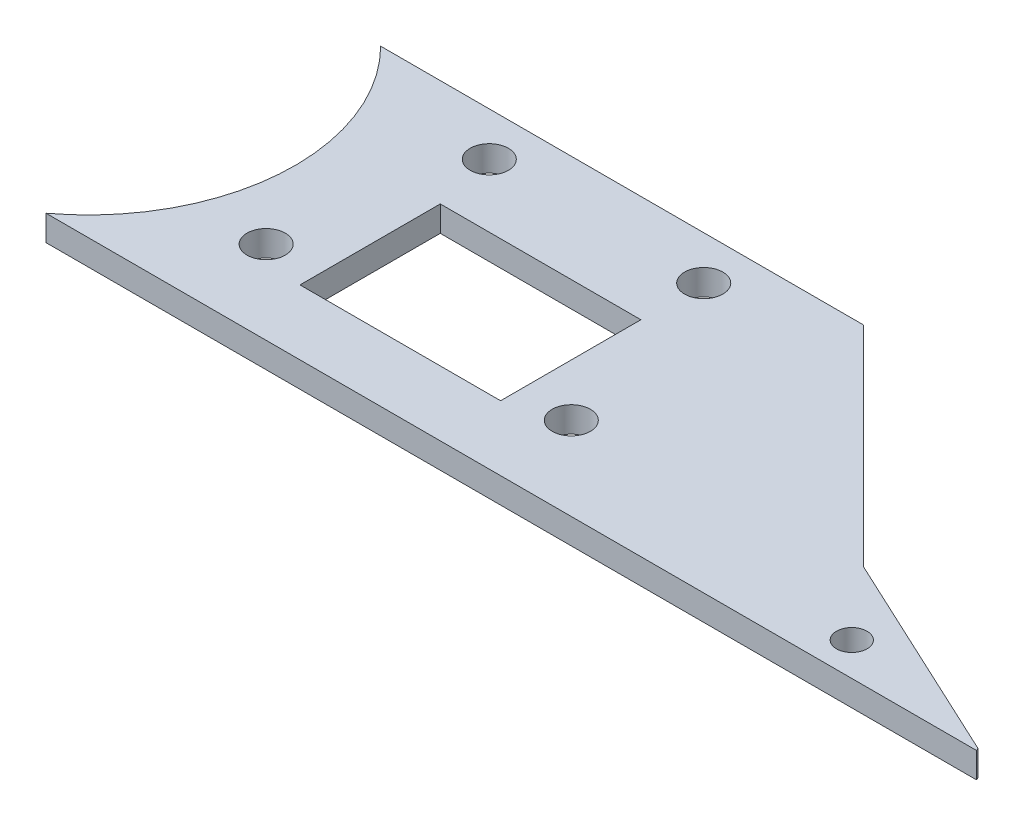
SolidWorks part; units mm, degrees
ref_plane "Спереди" through (0, 0, 0) normal (0, 0, 1) x (1, 0, 0)
ref_plane "Сверху" through (0, 0, 0) normal (0, 1, 0) x (1, 0, 0)
ref_plane "Справа" through (0, 0, 0) normal (1, 0, 0) x (0, 0, -1)
sketch "Эскиз1" plane through (0, 0, 0) normal (0, 1, 0) x (1, 0, 0)
  line L13 (-56.9238, -23.832) -> (16.3829, -23.832)
  line L14 (16.3829, -23.832) -> (-0.8369, -15.8022)
  line L15 (-0.8369, -15.8022) -> (-17.272, 0.6328)
  line L20 (-36.2092, 0.6328) -> (-36.2092, -23.832) construction
  line L25 (-26.3662, -7.7426) -> (-42.0968, -7.7426)
  line L28 (-55.1464, 0.6328) -> (-17.272, 0.6328)
  line L29 (-26.3662, -7.7426) -> (-26.3662, -18.7426)
  line L30 (-26.3662, -18.7426) -> (-42.0968, -18.7426)
  line L31 (-42.0968, -7.7426) -> (-42.0968, -18.7426)
  arc A1 (-51.7409, -17.2996) -> (-55.1464, 0.6328) centre (-66.6008, -10.832) ccw
  arc A2 (-56.9238, -23.832) -> (-51.7409, -17.2996) centre (-66.6008, -10.832) ccw
  circle A3 centre (-43.2057, -2.7898) radius 1.5
  circle A4 centre (-26.393, -2.7898) radius 1.5
  circle A5 centre (-46.1933, -17.2996) radius 1.5
  circle A6 centre (-22.2662, -17.2996) radius 1.5
  dimension "D1" = 15.7306
  dimension "D6" = 4.1
  dimension "D2" = 11
  dimension "D3" = 5.0894
  dimension "D4" = 6.5324
  dimension "D5" = 4.0965
  dimension "D7" = 24.4648
  dimension "D8" = 9.843
extrude "Бобышка-Вытянуть1" add sketch "Эскиз1" along normal blind 2
sketch "Эскиз2" plane through (0, 2, 0) normal (0, 1, 0) x (1, 0, 0)
  line L0 (16.3829, -23.832) -> (15.9601, -23.6348)
  line L1 (16.3829, -23.832) -> (-0.8369, -15.8022) construction
  line L2 (15.5753, -22.5775) -> (16.059, -23.9065) construction
  line L3 (15.9601, -23.6348) -> (16.059, -23.9065)
  line L4 (16.059, -23.9065) -> (-0.2545, -16.2993) construction
  line L5 (16.059, -23.9065) -> (16.3829, -23.832)
extrude "Вырез-Вытянуть1" cut sketch "Эскиз2" against normal through all and the other way blind 106.5
sketch "Эскиз5" plane through (0, 2, 0) normal (0, -1, 0) x (1, 0, 0)
  circle A0 centre (-22.2662, 17.2996) radius 1.5
sketch "Эскиз6" plane through (0, 2, 0) normal (0, -1, 0) x (1, 0, 0)
  circle A0 centre (-22.2662, 17.2996) radius 1.5
sketch "Эскиз7" plane through (0, 0, 0) normal (0, -1, 0) x (1, 0, 0)
  line L2 (-0.8369, 21.2247) -> (12.3982, 21.2247) construction
  circle A0 centre (3.6511, 21.2247) radius 1.2
extrude "Вырез-Вытянуть5" cut sketch "Эскиз7" against normal blind 15
sketch "Эскиз8" plane through (0, 2, 0) normal (0, -1, 0) x (1, 0, 0)
  circle A0 centre (3.6511, 21.2247) radius 1.5
